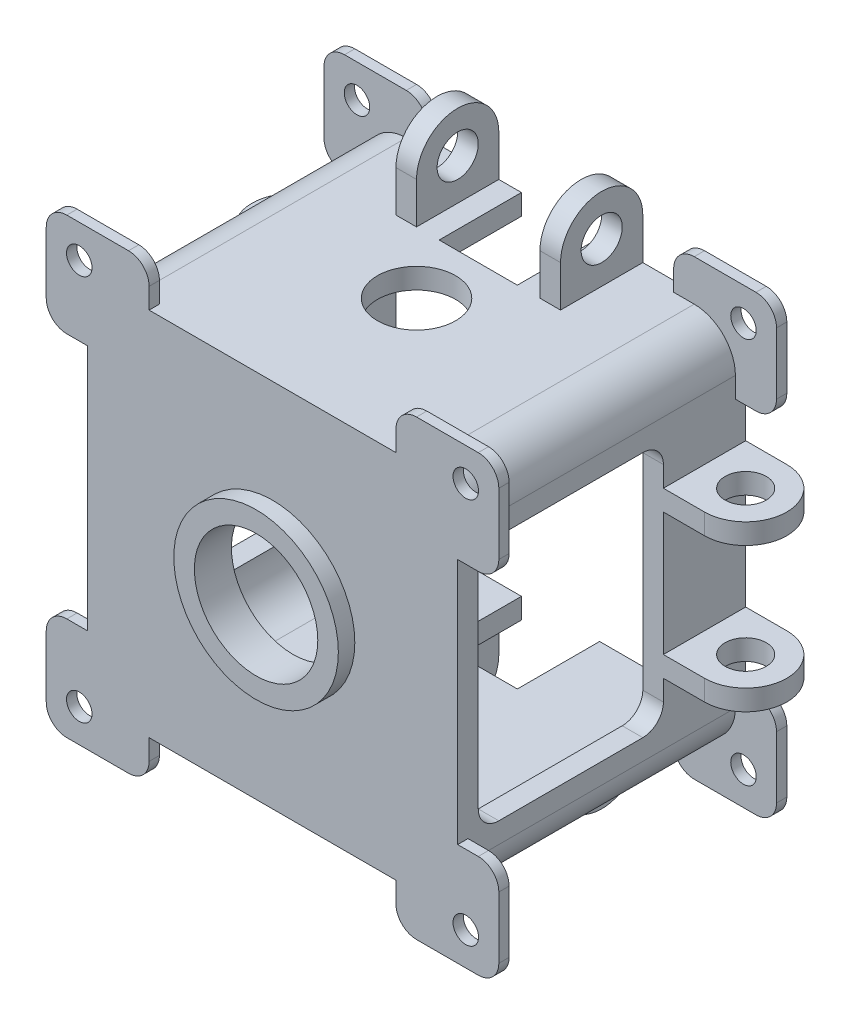
SolidWorks part; units mm, degrees
other "标注1"
sketch "草图6" plane through (67.5, -67.5, 0) normal (0.0299, -0.9992, -0.0283) x (0.0877, 0.0308, -0.9957)
material "2024 合金"
ref_plane "前视基准面" through (0, 0, 0) normal (0, 0, 1) x (1, 0, 0)
ref_plane "上视基准面" through (0, 0, 0) normal (0, 1, 0) x (1, 0, 0)
ref_plane "右视基准面" through (0, 0, 0) normal (1, 0, 0) x (0, 0, -1)
sketch "草图1" plane through (0, 0, 0) normal (0, 0, 1) x (1, 0, 0)
  line L1 (-35, -45) -> (35, -45)
  line L2 (-45, -35) -> (-45, 35)
  line L3 (-35, 45) -> (35, 45)
  line L4 (45, -35) -> (45, 35)
  line L5 (-45, -45) -> (45, 45) construction
  line L6 (-45, 45) -> (45, -45) construction
  line L7 (-30, -40) -> (30, -40)
  line L8 (-40, -30) -> (-40, 30)
  line L9 (-30, 40) -> (30, 40)
  line L10 (40, -30) -> (40, 30)
  line L11 (-40, -40) -> (40, 40) construction
  line L12 (-40, 40) -> (40, -40) construction
  arc A0 (35, -45) -> (45, -35) centre (35, -35) ccw
  arc A1 (30, -40) -> (40, -30) centre (30, -30) ccw
  arc A2 (-35, -45) -> (-45, -35) centre (-35, -35) cw
  arc A3 (-30, -40) -> (-40, -30) centre (-30, -30) cw
  arc A4 (-45, 35) -> (-35, 45) centre (-35, 35) cw
  arc A5 (35, 45) -> (45, 35) centre (35, 35) cw
  arc A6 (30, 40) -> (40, 30) centre (30, 30) cw
  arc A7 (-40, 30) -> (-30, 40) centre (-30, 30) cw
  point P0 (0, 0)
  point P7 (0, 0)
  dimension "D1" = 90
  dimension "D5" = 10
  dimension "D2" = 90
  dimension "D3" = 80
  dimension "D4" = 80
extrude "凸台-拉伸1" add sketch "草图1" along normal blind 70
sketch "草图3" plane through (0, 45, 0) normal (0, 1, 0) x (1, 0, 0)
  line L0 (0, 0) -> (0, -35) construction
  line L1 (35, 0) -> (-35, 0) construction
  line L2 (35, 0) -> (-35, 0) construction
  line L3 (9.5, 20) -> (-9.5, 20)
  line L4 (9.5, 20) -> (9.5, -20)
  line L5 (9.5, -20) -> (-9.5, -20)
  line L6 (-9.5, 20) -> (-9.5, -20)
  line L7 (9.5, 20) -> (-9.5, -20) construction
  line L8 (9.5, -20) -> (-9.5, 20) construction
  circle A0 centre (0, -35) radius 9.5
  dimension "D2" = 19
  dimension "D1" = 35
  dimension "D3" = 20
  dimension "D4" = 19
extrude "切除-拉伸2" cut sketch "草图3" against normal through all
sketch "草图4" plane through (0, -1.9977, 89.2652) normal (1, 0, 0) x (0, 0, -1)
  line L0 (69.2652, -42.0023) -> (69.2652, -53.0023)
  line L3 (89.2652, -53.0023) -> (89.2652, -42.0023)
  line L5 (89.2652, -42.0023) -> (69.2652, -42.0023)
  arc A0 (69.2652, -53.0023) -> (89.2652, -53.0023) centre (79.2652, -53.0023) ccw
  circle A1 centre (79.2652, -53.0023) radius 5
  dimension "D3" = 10
  dimension "D1" = 11
extrude "凸台-拉伸2" add sketch "草图4" along normal blind 20 and the other way blind 20
sketch "草图5" plane through (0, 0, 0) normal (0, 0, -1) x (-1, 0, 0)
  line L0 (0, 0) -> (0, -60.5) construction
  line L1 (15, -45) -> (-15, -45)
  line L2 (15, -45) -> (15, -76)
  line L3 (15, -76) -> (-15, -76)
  line L4 (-15, -45) -> (-15, -76)
  line L5 (15, -45) -> (-15, -76) construction
  line L6 (15, -76) -> (-15, -45) construction
  line L9 (-20, -45) -> (-35, -45) construction
  point P0 (0, -60.5)
  dimension "D1" = 30
  dimension "D2" = 31
extrude "切除-拉伸3" cut sketch "草图5" against normal up to surface (20 mm away) up to face at (0, -50, 20)
sketch "草图17" plane through (0, -44, 0) normal (0, 1, 0) x (1, 0, 0)
  line L1 (-9.5, -20) -> (9.5, -20)
  line L2 (-9.5, -20) -> (-9.5, 0)
  line L3 (-9.5, 0) -> (9.5, 0)
  line L4 (9.5, -20) -> (9.5, 0)
extrude "切除-拉伸7" cut sketch "草图17" against normal through all and the other way through all
ref_plane "基准面1" through (0, 0, 0) normal (0, -1, 0) x (-1, 0, 0)
ref_plane "基准面2" through (0, 0, 0) normal (1, 0, 0) x (0, 0, -1)
ref_axis "基准轴1" through (0, 0, 26.25) along (0, 0, -1)
pattern_circular "阵列(圆周)3" count 4 over 360 about axis through (0, 0, 26.25) along (0, 0, -1) of "切除-拉伸3", "凸台-拉伸2"
sketch "草图13" plane through (0, 0, 70) normal (0, 0, 1) x (1, 0, 0)
  line L1 (40, 40) -> (-40, 40)
  line L2 (40, 40) -> (40, -40)
  line L3 (40, -40) -> (-40, -40)
  line L4 (-40, 40) -> (-40, -40)
  line L5 (40, 40) -> (-40, -40) construction
  line L6 (40, -40) -> (-40, 40) construction
  circle A0 centre (0, 0) radius 15
  point P0 (0, 0)
  dimension "D3" = 30
  dimension "D1" = 80
  dimension "D2" = 80
extrude "凸台-拉伸3" add sketch "草图13" against normal blind 5
sketch "草图14" plane through (0, 0, 70) normal (0, 0, 1) x (1, 0, 0)
  circle A0 centre (0, 0) radius 15
  circle A1 centre (0, 0) radius 20
  dimension "D1" = 30
  dimension "D2" = 40
extrude "凸台-拉伸4" add sketch "草图14" along normal blind 4 and the other way blind 7.5
sketch "草图15" plane through (0, 0, 0) normal (0, 0, -1) x (-1, 0, 0)
  line L0 (-50, 50) -> (-30, 30) construction
  line L1 (-40, -30) -> (-40, 30) construction
  line L3 (-30, 40) -> (-9.5, 40) construction
  line L4 (-40, 30) -> (-50, 30)
  line L5 (-30, 40) -> (-30, 50)
  line L6 (-35, 55) -> (-50, 55)
  line L7 (-55, 35) -> (-55, 50)
  arc A0 (-30, 40) -> (-40, 30) centre (-30, 30) ccw construction
  arc A1 (-40, 30) -> (-30, 40) centre (-30, 30) cw
  arc A2 (-50, 55) -> (-55, 50) centre (-50, 50) ccw
  arc A3 (-30, 50) -> (-35, 55) centre (-35, 50) ccw
  arc A4 (-50, 30) -> (-55, 35) centre (-50, 35) cw
  circle A6 centre (-46.9706, 46.9706) radius 3.1
  point P17 (-55, 55)
  point P20 (-30, 55)
  point P23 (-55, 30)
  dimension "D3" = 5
  dimension "D4" = 6.2
  dimension "D1" = 25
  dimension "D2" = 25
  dimension "D5" = 24
extrude "凸台-拉伸5" add sketch "草图15" against normal blind 2.5
mirror "镜向2" about plane through (0, 0, 0) normal (1, 0, 0) of "凸台-拉伸5"
mirror "镜向3" about plane through (0, 0, 0) normal (0, -1, 0) of "镜向2"
sketch "草图16" plane through (-45, 0, 0) normal (-1, 0, 0) x (0, 0, 1)
  line L0 (20, -15) -> (20, -20) construction
  line L1 (25, 30) -> (60, 30)
  line L2 (20, 25) -> (20, -25)
  line L3 (25, -30) -> (60, -30)
  line L4 (65, 25) -> (65, -25)
  line L5 (20, 30) -> (65, -30) construction
  line L6 (20, -30) -> (65, 30) construction
  line L7 (70, 35) -> (70, -35) construction
  line L8 (0, 0) -> (42.5, 0) construction
  arc A0 (60, 30) -> (65, 25) centre (60, 25) cw
  arc A1 (25, 30) -> (20, 25) centre (25, 25) ccw
  arc A2 (20, -25) -> (25, -30) centre (25, -25) ccw
  arc A3 (60, -30) -> (65, -25) centre (60, -25) ccw
  point P0 (42.5, 0)
  dimension "D3" = 5
  dimension "D1" = 5
  dimension "D2" = 60
extrude "切除-拉伸6" cut sketch "草图16" against normal through all
sketch "草图18" plane through (0, 44, 0) normal (0, -1, 0) x (1, 0, 0)
  line L1 (9.5, 20) -> (-9.5, 20)
  line L2 (9.5, 20) -> (9.5, 0)
  line L3 (9.5, 0) -> (-9.5, 0)
  line L4 (-9.5, 20) -> (-9.5, 0)
extrude "切除-拉伸8" cut sketch "草图18" against normal through all
sketch "草图21" plane through (0, 0, 70) normal (0, 0, 1) x (1, 0, 0)
  line L0 (-35, 45) -> (-30, 45)
  line L1 (-30, 45) -> (-30, 50)
  line L2 (-35, 55) -> (-50, 55)
  line L3 (-55, 50) -> (-55, 35)
  line L4 (-50, 30) -> (-45, 30)
  line L5 (-45, 30) -> (-45, 35)
  line L6 (-45, -35) -> (-45, -30)
  line L7 (-45, -30) -> (-50, -30)
  line L8 (-55, -35) -> (-55, -50)
  line L9 (-50, -55) -> (-35, -55)
  line L10 (-30, -50) -> (-30, -45)
  line L11 (-30, -45) -> (-35, -45)
  line L12 (-45, -35) -> (-45, -30)
  line L13 (-45, -30) -> (-50, -30)
  line L14 (-55, -35) -> (-55, -50)
  line L15 (-50, -55) -> (-35, -55)
  line L16 (-30, -50) -> (-30, -45)
  line L17 (-30, -45) -> (-35, -45)
  line L18 (45, 35) -> (45, 30)
  line L19 (45, 30) -> (50, 30)
  line L20 (55, 35) -> (55, 50)
  line L21 (50, 55) -> (35, 55)
  line L22 (30, 50) -> (30, 45)
  line L23 (30, 45) -> (35, 45)
  line L24 (35, -45) -> (30, -45)
  line L25 (30, -45) -> (30, -50)
  line L26 (35, -55) -> (50, -55)
  line L27 (55, -50) -> (55, -35)
  line L28 (50, -30) -> (45, -30)
  line L29 (45, -30) -> (45, -35)
  circle A0 centre (-46.9706, -46.9706) radius 3.1 construction
  circle A1 centre (-46.9706, -46.9706) radius 3.1
  circle A2 centre (-46.9706, 46.9706) radius 3.1
  arc A3 (-30, 50) -> (-35, 55) centre (-35, 50) ccw
  arc A4 (-50, -30) -> (-55, -35) centre (-50, -35) ccw
  arc A5 (-55, -50) -> (-50, -55) centre (-50, -50) ccw
  arc A6 (-35, -55) -> (-30, -50) centre (-35, -50) ccw
  arc A7 (-45, -35) -> (-35, -45) centre (-35, -35) ccw
  arc A8 (-50, -30) -> (-55, -35) centre (-50, -35) ccw
  arc A9 (-55, -50) -> (-50, -55) centre (-50, -50) ccw
  arc A10 (-35, -55) -> (-30, -50) centre (-35, -50) ccw
  arc A11 (-45, -35) -> (-35, -45) centre (-35, -35) ccw
  arc A12 (-50, 55) -> (-55, 50) centre (-50, 50) ccw
  arc A13 (-55, 35) -> (-50, 30) centre (-50, 35) ccw
  arc A14 (-35, 45) -> (-45, 35) centre (-35, 35) ccw
  circle A15 centre (46.9706, 46.9706) radius 3.1
  arc A16 (50, 30) -> (55, 35) centre (50, 35) ccw
  arc A17 (55, 50) -> (50, 55) centre (50, 50) ccw
  arc A18 (35, 55) -> (30, 50) centre (35, 50) ccw
  arc A19 (45, 35) -> (35, 45) centre (35, 35) ccw
  circle A20 centre (46.9706, -46.9706) radius 3.1
  arc A21 (30, -50) -> (35, -55) centre (35, -50) ccw
  arc A22 (50, -55) -> (55, -50) centre (50, -50) ccw
  arc A23 (55, -35) -> (50, -30) centre (50, -35) ccw
  arc A24 (35, -45) -> (45, -35) centre (35, -35) ccw
  dimension "D1" = 0
  dimension "D2" = 4
extrude "凸台-拉伸6" add sketch "草图21" against normal blind 2.5
